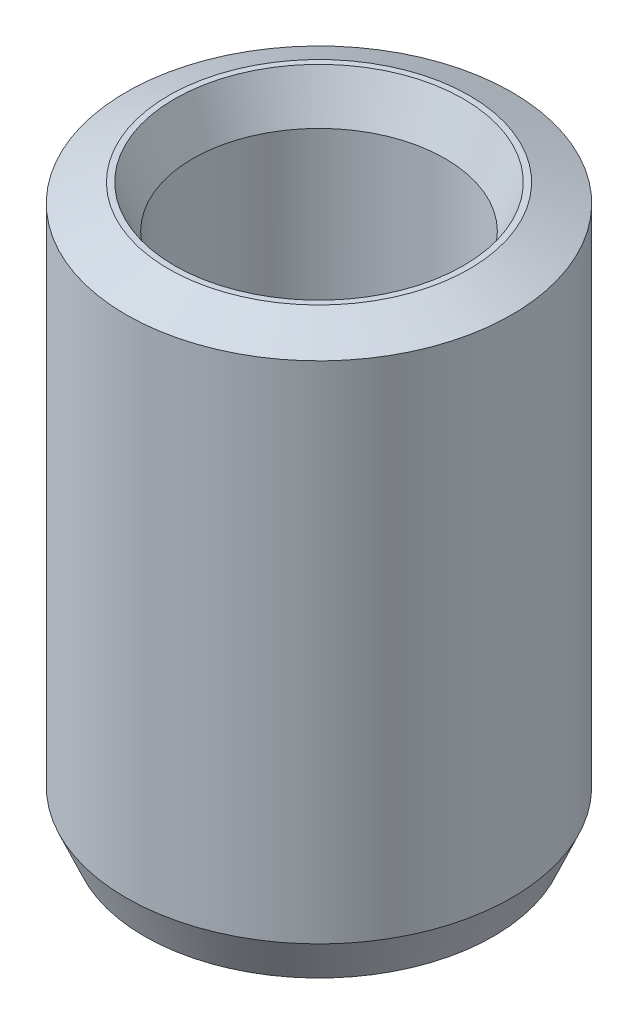
SolidWorks part; units mm, degrees
ref_plane "Front Plane" through (0, 0, 0) normal (0, 0, 1) x (1, 0, 0)
ref_plane "Top Plane" through (0, 0, 0) normal (0, 1, 0) x (1, 0, 0)
ref_plane "Right Plane" through (0, 0, 0) normal (1, 0, 0) x (0, 0, -1)
sketch "Sketch1" plane through (0, 0, 0) normal (0, 1, 0) x (1, 0, 0)
  circle A0 centre (0, 0) radius 35
  dimension "SLEEVE_OD" = 70
extrude "Boss-Extrude1" add sketch "Sketch1" along normal blind 102.685
sketch "Sketch2" plane through (0, 0, 0) normal (0, 1, 0) x (1, 0, 0)
  circle A0 centre (0, 0) radius 22.8918
  dimension "BORE_D" = 45.7835
extrude "Cut-Extrude1" cut sketch "Sketch2" along normal through all
chamfer "Chamfer1" distance 3.326 angle 66.678 4 edges at (0, 102.685, 22.8918) (0, 0, 22.8918) (0, 0, 35) (0, 102.685, 35) first distance on face at (0, 102.685, 22.8918) first distance on face at (0, 0, 22.8918) first distance on face at (0, 102.685, 35)
